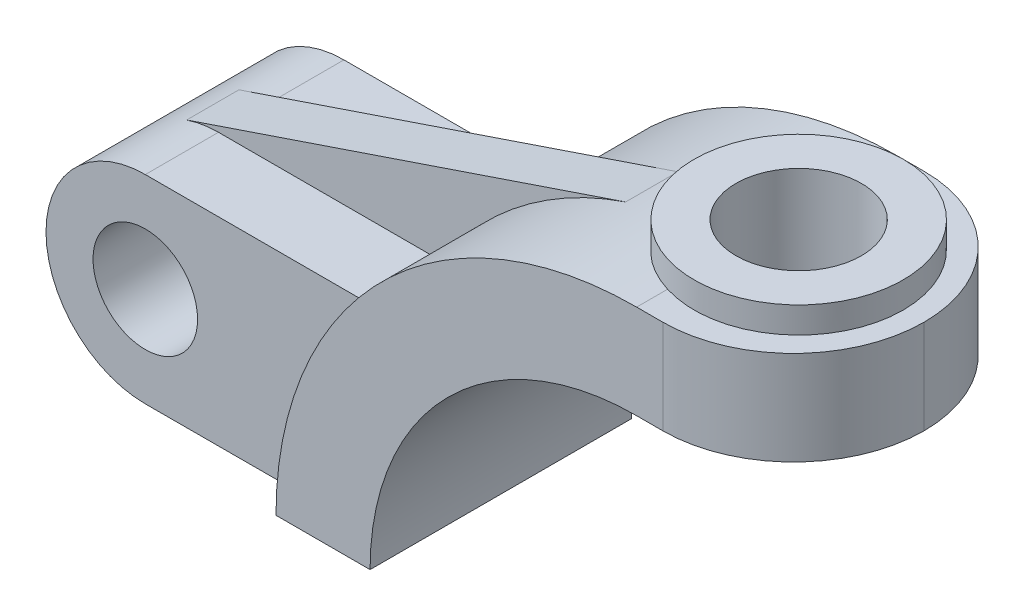
SolidWorks part; units mm, degrees
material "Borracha de silicone"
ref_plane "Plano frontal" through (0, 0, 0) normal (0, 0, 1) x (1, 0, 0)
ref_plane "Plano superior" through (0, 0, 0) normal (0, 1, 0) x (1, 0, 0)
ref_plane "Plano direito" through (0, 0, 0) normal (1, 0, 0) x (0, 0, -1)
sketch "Esboço1" plane through (0, 0, 0) normal (0, 0, 1) x (1, 0, 0)
  line L0 (-51, 0) -> (-69, 0)
  line L1 (0, 51) -> (0, 69)
  line L2 (-100, -0.04) -> (-69, 0)
  line L3 (0, 69) -> (30, 69)
  line L4 (-22.1073, 65.3626) -> (-106.0875, 36.9584)
  line L5 (-100, 37.96) -> (-57.6198, 37.96)
  line L6 (30, 69) -> (30, 51)
  line L7 (30, 51) -> (0, 51)
  arc A0 (0, 51) -> (-51, 0) centre (0, 0) ccw
  arc A1 (0, 69) -> (-69, 0) centre (0, 0) ccw
  circle A2 centre (-100, 18.96) radius 19
  circle A3 centre (-100, 18.96) radius 10
  dimension "D1" = 51
  dimension "D2" = 18
  dimension "D3" = 38
  dimension "D5" = 20
  dimension "D4" = 30
extrude "Ressalto-extrusão3" add sketch "Esboço1" along normal blind 25 and the other way blind 25 contours L1 A1 L0 A0 region at (-38.4837, 38.4837, 0)
extrude "Ressalto-extrusão4" add sketch "Esboço1<3>" along normal blind 19 and the other way blind 19 separate body contours A2 L2 A3 region at (-118.2177, 15.9625, 0)
sketch "Esboço1<3>" plane through (0, 0, 0) normal (0, 0, 1) x (1, 0, 0) same geometry as "Esboço1"
extrude "Ressalto-extrusão6" add sketch "Esboço1<5>" along normal blind 19 and the other way blind 19 contours A2 L2 A1 L5 region at (-75.3799, 20.769, 0)
sketch "Esboço1<5>" plane through (0, 0, 0) normal (0, 0, 1) x (1, 0, 0) same geometry as "Esboço1"
extrude "Ressalto-extrusão7" add sketch "Esboço1<6>" along normal blind 5 and the other way blind 5 contours A2 L5 A1 L4 region at (-65.4384, 45.8163, 0)
sketch "Esboço1<6>" plane through (0, 0, 0) normal (0, 0, 1) x (1, 0, 0) same geometry as "Esboço1"
extrude "Ressalto-extrusão8" add sketch "Esboço1<7>" along normal blind 25 and the other way blind 25 contours L7 L6 L3 L1 region at (15, 60, 0)
sketch "Esboço1<7>" plane through (0, 0, 0) normal (0, 0, 1) x (1, 0, 0) same geometry as "Esboço1"
fillet "Filete1" radius 25 2 edges at (30, 60, -25) (30, 60, 25)
sketch "Esboço3" plane through (0, 0, 0) normal (0, 1, 0) x (1, 0, 0)
  circle A1 centre (6, 0) radius 20
  arc A2 (5, -25) -> (30, 0) centre (5, 0) ccw construction
  dimension "D1" = 40
  dimension "D2" = 0
  dimension "D3" = 6
extrude "Ressalto-extrusão9" add sketch "Esboço3" along normal blind 5 and the other way blind 15 from surface starting at face at (10.0711, 69, 0)
sketch "Esboço4" plane through (0, 74, 0) normal (0, 1, 0) x (1, 0, 0)
  circle A1 centre (6, 0) radius 12
  dimension "D1" = 24
extrude "Corte-extrusão1" cut sketch "Esboço4" against normal blind 80
